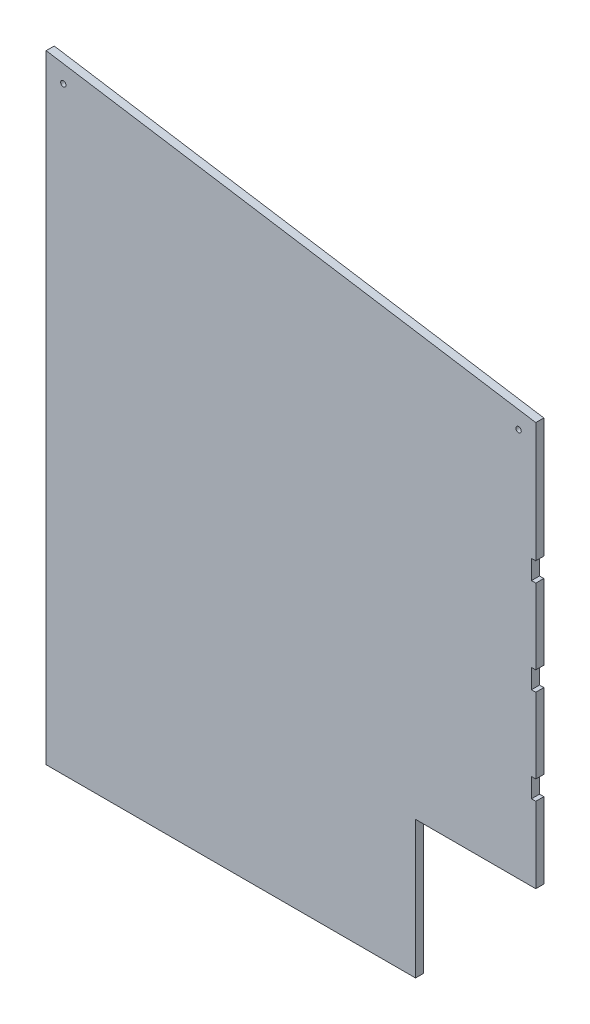
SolidWorks part; units mm, degrees
material "Pine"
ref_plane "Front Plane" through (0, 0, 0) normal (0, 0, 1) x (1, 0, 0)
ref_plane "Top Plane" through (0, 0, 0) normal (0, 1, 0) x (1, 0, 0)
ref_plane "Right Plane" through (0, 0, 0) normal (1, 0, 0) x (0, 0, -1)
sketch "Sketch1" plane through (0, 0, 0) normal (0, 0, 1) x (1, 0, 0)
  line L0 (491.3289, -397.2664) -> (491.3289, 199.6336) construction
  line L2 (-232.5711, 313.9336) -> (-232.5711, -600.4664)
  line L3 (-232.5711, -600.4664) -> (313.5289, -600.4664)
  line L4 (491.3289, 199.6336) -> (491.3289, -397.2664)
  line L7 (491.3289, -397.2664) -> (313.5289, -397.2664)
  line L8 (313.5289, -600.4664) -> (313.5289, -397.2664)
  line L9 (491.3289, 199.6336) -> (-232.5711, 313.9336)
  dimension "D1" = 203.2
  dimension "D2" = 177.8
  dimension "D3" = 914.4
  dimension "D4" = 723.9
  dimension "D5" = 596.9
extrude "Boss-Extrude1" add sketch "Sketch1" along normal blind 11.9062
sketch "Sketch2" plane through (0, 0, 11.9062) normal (0, 0, 1) x (1, 0, 0)
  line L0 (491.3289, -397.2664) -> (491.3289, 199.6336) construction
  line L1 (491.3289, -285.3159) -> (484.9789, -285.3159)
  line L2 (491.3289, -285.3159) -> (491.3289, -256.7409)
  line L3 (491.3289, -256.7409) -> (484.9789, -256.7409)
  line L4 (484.9789, -285.3159) -> (484.9789, -256.7409)
  line L5 (313.5289, -397.2664) -> (491.3289, -397.2664) construction
  line L6 (491.3289, -145.6159) -> (484.9789, -145.6159)
  line L7 (491.3289, -145.6159) -> (491.3289, -117.0409)
  line L8 (491.3289, -117.0409) -> (484.9789, -117.0409)
  line L9 (484.9789, -145.6159) -> (484.9789, -117.0409)
  line L10 (491.3289, -5.9159) -> (484.9789, -5.9159)
  line L11 (491.3289, -5.9159) -> (491.3289, 22.6591)
  line L12 (491.3289, 22.6591) -> (484.9789, 22.6591)
  line L13 (484.9789, -5.9159) -> (484.9789, 22.6591)
  point P14 (484.9789, -271.0284)
  point P17 (484.9789, -131.3284)
  point P18 (484.9789, 8.3716)
  dimension "D1" = 28.575
  dimension "D2" = 6.35
  dimension "D3" = 126.238
  dimension "D4" = 265.938
  dimension "D5" = 405.638
extrude "Cut-Extrude1" cut sketch "Sketch2" against normal through all
hole_wizard "5/16 (0.3125) Diameter Hole1" positions "Sketch3" profile "Sketch4" hole size "5/16" standard "ANSI Inch" end condition through all
sketch "Sketch3" plane through (0, 0, 0) normal (0, 0, -1) x (-1, 0, 0)
  line L0 (-491.3289, 199.6336) -> (232.5711, 313.9336) construction
  line L1 (232.5711, 313.9336) -> (232.5711, -600.4664) construction
  line L2 (-491.3289, 22.6591) -> (-491.3289, 199.6336) construction
  point P0 (207.1711, 284.2084)
  point P2 (-465.9289, 177.9295)
  dimension "D1" = 25.4
  dimension "D2" = 25.4
  dimension "D3" = 25.4
  dimension "D4" = 25.4
sketch "Sketch4" plane through (-207.1711, 284.2084, 0) normal (1, 0, 0) x (0, 1, 0)
  line L0 (0, 0) -> (0, 11.9062)
  line L1 (0, 11.9062) -> (3.9687, 11.9062)
  line L2 (3.9687, 11.9062) -> (3.9687, 0)
  line L5 (3.9687, 0) -> (0, 0)
  line L11 (0, -6.35) -> (0, 107.95) construction
  dimension "Thru Hole Dia." = 7.9375
  dimension "Thru Hole Depth" = 11.9062
